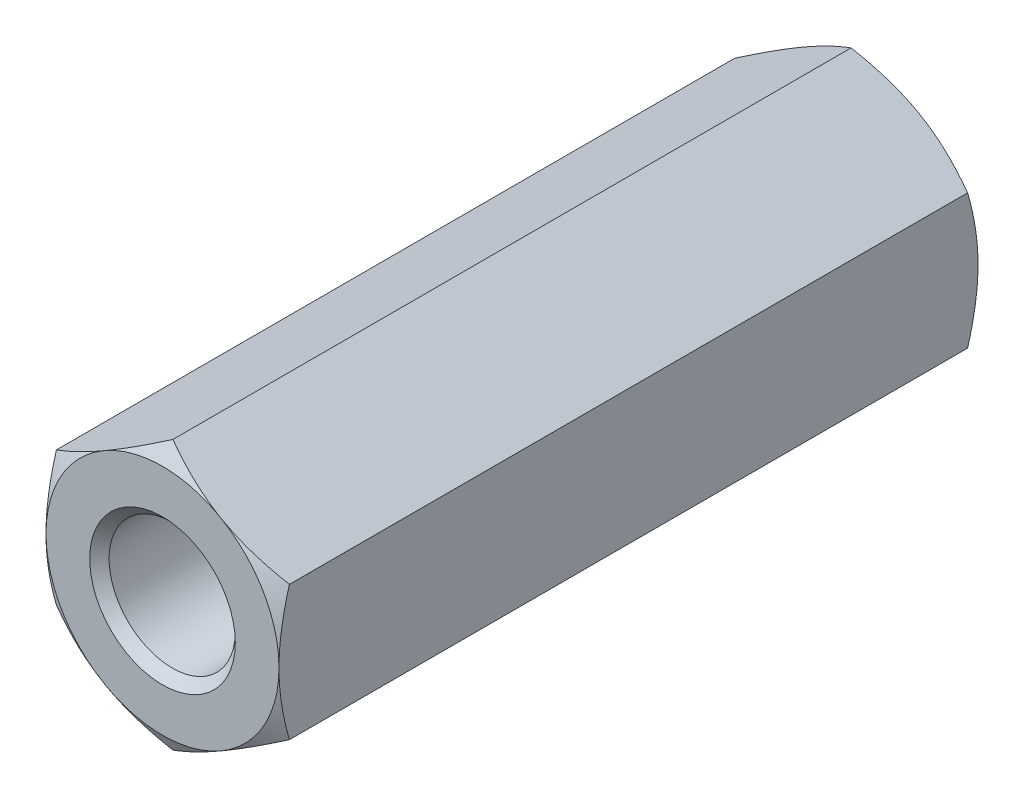
SolidWorks part; units mm, degrees
ref_plane "Front Plane" through (0, 0, 0) normal (0, 0, 1) x (1, 0, 0)
ref_plane "Top Plane" through (0, 0, 0) normal (0, 1, 0) x (1, 0, 0)
ref_plane "Right Plane" through (0, 0, 0) normal (1, 0, 0) x (0, 0, -1)
sketch "Sketch0" plane through (0, 0, 0) normal (1, 0, 0) x (0, 0, -1)
  line L0 (-9, 0) -> (9, 0) construction
  line L1 (0, 3) -> (0, -3) construction
  line L2 (-9, 1.625) -> (-9, -1.625) construction
  line L3 (9, 1.625) -> (9, -1.625) construction
  line L4 (-9, 3) -> (9, 3) construction
  line L5 (0, 1.625) -> (0, -1.625) construction
  line L6 (-9.4687, 1.6791) -> (-8.9687, 1.6791) construction
  line L7 (-8.9687, 1.6791) -> (-9.2187, 1.2461) construction
  line L8 (-9.2187, 1.2461) -> (-9.4687, 1.6791) construction
  line L9 (-9.2187, 1.2461) -> (-9.2187, 1.3002) construction
  line L10 (-9.4375, 1.625) -> (-9, 1.625) construction
  line L11 (-9.2187, 1.625) -> (-9.2187, 1.6791) construction
  line L12 (-9.25, 1.3002) -> (-9.1875, 1.3002) construction
  line L13 (-9.2187, 1.6521) -> (-9.4531, 1.6521) construction
  line L14 (-9.2187, 1.6521) -> (-8.9844, 1.6521) construction
  line L15 (-9, 1.3002) -> (-9, -1.3002) construction
  point P13 (0, 0)
  point P24 (-9, -1.625)
  point P29 (-9, -1.3002)
  dimension "Thread Size" = 3.25
  dimension "Length" = 18
  dimension "Width" = 6
  dimension "Pitch" = 0.5
  dimension "D1" = 0.0625
sketch "Sketch1" plane through (0, 0, 0) normal (0, 0, 1) x (1, 0, 0)
  line L0 (0, 0) -> (-0.6219, -1.5013) construction
  line L1 (0, 3.4641) -> (-3, 1.7321)
  line L2 (-3, 1.7321) -> (-3, -1.7321)
  line L3 (-3, -1.7321) -> (0, -3.4641)
  line L4 (0, -3.4641) -> (3, -1.7321)
  line L5 (3, -1.7321) -> (3, 1.7321)
  line L6 (3, 1.7321) -> (0, 3.4641)
  circle A0 centre (0, 0) radius 3 construction
  circle A1 centre (0, 0) radius 1.625
  point P11 (-0.6219, -1.5013)
  dimension "D1" = 22.5
extrude "Boss-Extrude1" add sketch "Sketch1" against normal up to vertex (-9 mm away) and the other way up to vertex (-9 mm away) up to point (0, 0, 9) other way up to point (0, 0, -9)
sketch "Sketch2" plane through (0, 0, -9) normal (0, 0, -1) x (-1, 0, 0)
  circle A0 centre (0, 0) radius 3 construction
  circle A1 centre (0, 0) radius 3
extrude "Cut-Extrude1" cut sketch "Sketch2" against normal through all draft 60 flip side to cut
sketch "Sketch3" plane through (0, 0, 9) normal (0, 0, 1) x (1, 0, 0)
  circle A0 centre (0, 0) radius 3 construction
  circle A1 centre (0, 0) radius 3
extrude "Cut-Extrude2" cut sketch "Sketch3" against normal through all draft 60 flip side to cut
chamfer "Chamfer1" distance 0.25 angle 45 2 edges at (1.625, 0, -9) (1.625, 0, 9)
sketch "Sketch4" plane through (0, 0, 9) normal (0, 0, 1) x (1, 0, 0)
  circle A0 centre (0, 0) radius 1.625 construction
  circle A1 centre (0, 0) radius 1.625
ref_axis "Center Axis 1" through (0, 0, -8.75) along (0, 0, 1)
curve "Helix/Spiral1" pitch 0.5 height 18.5 turns 37 parameters "Pitch"=0.5
sketch "Sketch10" plane through (0, 0, 0) normal (1, 0, 0) x (0, 0, -1)
  line L0 (-8.75, 1.625) -> (0.025, 1.625)
  line L1 (0.025, 1.625) -> (0.025, -1.625)
  line L2 (0.025, -1.625) -> (-8.75, -1.625)
  line L3 (0.225, 1.625) -> (0.225, -1.625)
  line L4 (0.225, -1.625) -> (9, -1.625)
  line L5 (0.225, 1.625) -> (9, 1.625)
  dimension "D1" = 8.775
sketch "Sketch5" plane through (0, 0, 0) normal (1, 0, 0) x (0, 0, -1)
  line L0 (-9.4531, 1.6521) -> (-8.9844, 1.6521)
  line L1 (-8.9844, 1.6521) -> (-9.1875, 1.3002)
  line L2 (-9.1875, 1.3002) -> (-9.25, 1.3002)
  line L3 (-9.25, 1.3002) -> (-9.4531, 1.6521)
equation "\"D3@Helix/Spiral1\"=\"Length@Sketch0\"+\"Pitch@Sketch0\""
equation "\"D1@Sketch10\"=(\"Length@Sketch0\"/2)*.975"
equation "\"D1@Sketch0\"=\"Pitch@Sketch0\"/8"
equation "\"D1@Chamfer1\"=\"Pitch@Sketch0\"*.5"
equation "\"Pitch@Helix/Spiral1\"=\"Pitch@Sketch0\""
